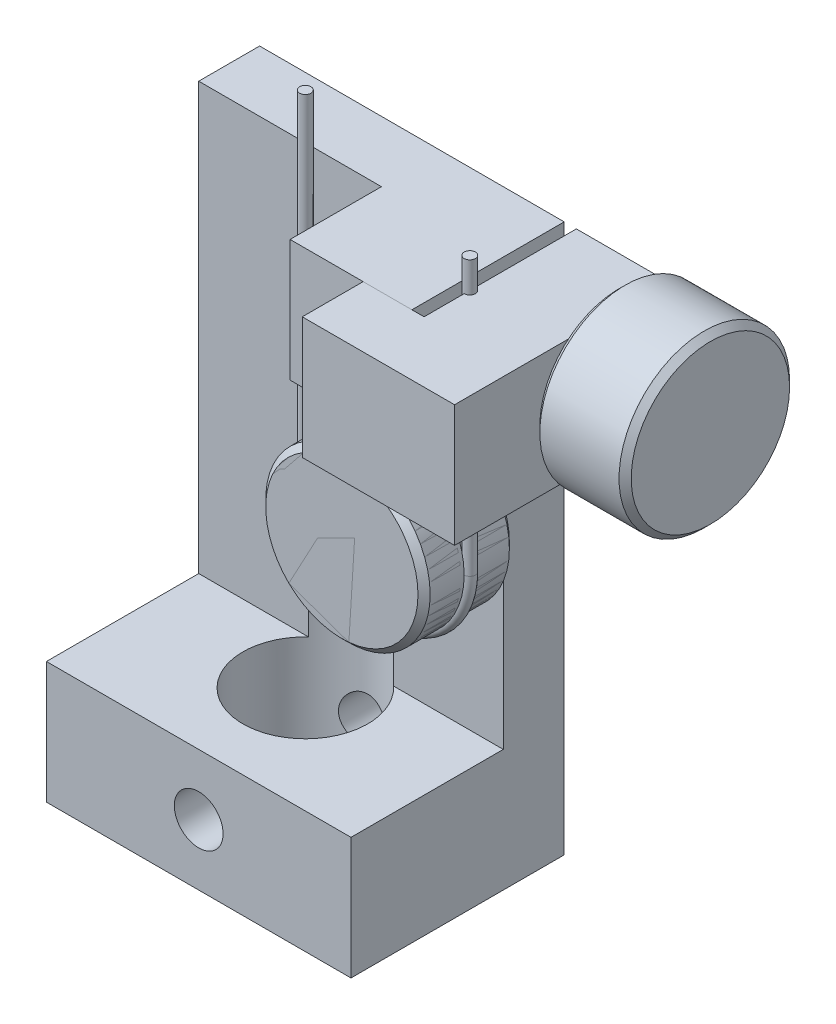
SolidWorks part; units mm, degrees
note: The reader was unsure of these and kept them because the rebuilt part matched: shared geometry of "Sketch5<3>", "Sketch10<3>", "Sketch14<5>", "Sketch19<3>".
other "Clamp"
other "Base"
other "2,85mm"
other "1,75mm"
other "Fastener"
ref_plane "Front Plane" through (0, 0, 0) normal (0, 0, 1) x (1, 0, 0)
ref_plane "Top Plane" through (0, 0, 0) normal (0, 1, 0) x (1, 0, 0)
ref_plane "Right Plane" through (0, 0, 0) normal (1, 0, 0) x (0, 0, -1)
sketch "Sketch1" plane through (0, 0, 0) normal (0, 0, 1) x (1, 0, 0)
  line L1 (25, -45) -> (-25, -45)
  line L2 (25, -45) -> (25, 45)
  line L3 (25, 45) -> (-25, 45)
  line L4 (-25, -45) -> (-25, 45)
  line L5 (0, 45) -> (0, -45) construction
  line L6 (25, 0) -> (-25, 0) construction
  point P0 (0, 0)
  dimension "D1" = 50
  dimension "D2" = 90
extrude "Boss-Extrude1" add sketch "Sketch1" along normal blind 10
sketch "Sketch2" plane through (0, 0, 10) normal (0, 0, 1) x (1, 0, 0)
  line L0 (-25, 45) -> (-25, -45) construction
  line L1 (-25, -25) -> (25, -25)
  line L2 (-25, -25) -> (-25, -45)
  line L3 (-25, -45) -> (25, -45)
  line L4 (25, -25) -> (25, -45)
  dimension "D1" = 20
extrude "Boss-Extrude2" add sketch "Sketch2" along normal blind 25
sketch "Sketch3" plane through (0, -25, 0) normal (0, 1, 0) x (1, 0, 0)
  line L1 (25, -10) -> (-25, -10) construction
  line L2 (0, 0) -> (0, -35) construction
  line L3 (25, 0) -> (-25, 0) construction
  line L4 (25, -35) -> (-25, -35) construction
  circle A0 centre (0, -17.5) radius 10.25
  point P9 (0, -10)
  dimension "D1" = 20.5
extrude "Cut-Extrude1" cut sketch "Sketch3" against normal through all and the other way blind 5
sketch "Sketch4" plane through (0, 0, 35) normal (0, 0, 1) x (1, 0, 0)
  line L0 (0, -25) -> (0, -45) construction
  line L2 (-25, -45) -> (25, -45) construction
  line L3 (25, -25) -> (-25, -25) construction
  circle A0 centre (0, -35) radius 4
  dimension "D1" = 8
  dimension "D2" = 10
extrude "Cut-Extrude2" cut sketch "Sketch4" against normal through all
sketch "Sketch5" plane through (0, 0, 10) normal (0, 0, 1) x (1, 0, 0)
  line L0 (0, -45) -> (0, 45) construction
  line L1 (-25, -45) -> (25, -45) construction
  line L2 (25, 45) -> (-25, 45) construction
  line L3 (25, -25) -> (25, 45) construction
  line L4 (25, 45) -> (5, 45)
  line L5 (25, 45) -> (25, 25)
  line L6 (25, 25) -> (5, 25)
  line L7 (5, 45) -> (5, 25)
  circle A0 centre (13.5, 5) radius 4.25
  circle A1 centre (13.5, 5) radius 12.075 construction
  line M9 (25, -25) -> (25, 45)
  line M10 (25, 45) -> (-25, 45)
  dimension "D1" = 8.5
  dimension "D5" = 1.425
  dimension "D2" = 20
  dimension "D3" = 20
  dimension "D4" = 20
  dimension "D6" = 11.5
extrude "Cut-Extrude3" cut sketch "Sketch5" against normal blind 30 contours A0
extrude "Boss-Extrude3" add sketch "Sketch5<3>" along normal blind 15 contours L7 L6 M10 M9
sketch "Sketch5<3>" plane through (0, 0, 10) normal (0, 0, 1) x (1, 0, 0) same geometry as "Sketch5"
sketch "Sketch9" plane through (0, 45, 0) normal (0, 1, 0) x (1, 0, 0)
  line L1 (27, 0) -> (42, 0)
  line L2 (27, 0) -> (27, -25)
  line L3 (27, -25) -> (42, -25)
  line L4 (42, 0) -> (42, -25)
  line L5 (25, 0) -> (-25, 0) construction
  line L6 (25, -25) -> (25, 0) construction
  line L7 (25, -25) -> (5, -25) construction
  dimension "D1" = 15
  dimension "D2" = 2
extrude "Boss-Extrude4" add sketch "Sketch9" against normal up to surface (20 mm away) separate body up to face at (15, 25, 17.5)
sketch "Sketch10" plane through (42, 0, 0) normal (1, 0, 0) x (0, 0, -1)
  line L0 (-22.5, -25) -> (-22.5, 45) construction
  line L1 (-35, -25) -> (-10, -25) construction
  line L2 (-25, 45) -> (0, 45) construction
  line L3 (0, -45) -> (0, 45) construction
  line L4 (-25, 25) -> (-25, 45) construction
  line L5 (-25, 35) -> (0, 35) construction
  line L6 (0, 25) -> (0, 45) construction
  line L7 (-17.5, 25) -> (-17.5, 45) construction
  line L8 (-25, 25) -> (-10, 25) construction
  line L9 (-25, 45) -> (0, 45) construction
  line L11 (-19, 45) -> (-16, 45) construction
  line L12 (-19, 45) -> (-19, 25) construction
  line L13 (-19, 25) -> (-16, 25) construction
  line L14 (-16, 45) -> (-16, 25) construction
  circle A0 centre (-8, 35) radius 4.25
  circle A1 centre (-8, 35) radius 5
  dimension "D1" = 8.5
  dimension "D4" = 10
  dimension "D2" = 8
  dimension "D3" = 3
extrude "Cut-Extrude4" cut sketch "Sketch10" against normal blind 27 contours A0
extrude "Cut-Extrude5" cut sketch "Sketch10<3>" against normal up to next (15 mm away)
sketch "Sketch10<3>" plane through (42, 0, 0) normal (1, 0, 0) x (0, 0, -1) same geometry as "Sketch10"
sketch "Sketch14" plane through (0, 0, 10) normal (0, 0, 1) x (1, 0, 0)
  line L0 (0, 45) -> (0, -45) construction
  line L1 (5, 45) -> (-25, 45) construction
  line L2 (-25, -45) -> (25, -45) construction
  circle A0 centre (13.5, 5) radius 13.5
  circle A3 centre (13.5, 5) radius 4.925
  circle M2 centre (13.5, 5) radius 4.25
  line M8 (25, -25) -> (25, 25)
  dimension "D1" = 27
  dimension "D2" = 9.85
extrude "Boss-Extrude5" add sketch "Sketch14" along normal up to surface (15 mm away) separate body contours M2 | A3 M2 | A0 A3 M8
extrude "Boss-Extrude8" add sketch "Sketch14<5>" against normal up to surface (10 mm away) contours M2 | A3 M2 up to face at (17.75, 5, 0)
sketch "Sketch14<5>" plane through (0, 0, 10) normal (0, 0, 1) x (1, 0, 0) same geometry as "Sketch14"
sketch "Sketch16" plane through (0, 0, 25) normal (0, 0, 1) x (1, 0, 0)
  line L0 (27, 5) -> (0, 5) construction
  circle A0 centre (13.5, 5) radius 13.5 construction
ref_plane "Plane4" through (0, 5, 0) normal (0, 1, 0) x (-1, 0, 0)
sketch "Sketch17" plane through (0, 5, 0) normal (0, 1, 0) x (-1, 0, 0)
  line L0 (0, 17.5) -> (-27, 17.5) construction
  line L1 (0, 10) -> (0, 25) construction
  line L2 (-27, 25) -> (-27, 10) construction
  line L3 (0, 18.425) -> (0, 17.5) construction
  line L6 (-13.5, 25) -> (-13.5, 0) construction
  line L7 (-27, 25) -> (0, 25) construction
  line L8 (-25, 0) -> (25, 0) construction
  line L9 (0, 18.425) -> (0, 16.575)
  arc A0 (0, 18.425) -> (0, 16.575) centre (0, 17.5) ccw
  dimension "D1" = 1.85
revolve "Cut-Revolve1" cut sketch "Sketch17" angle 360 about L6
sketch "Sketch18" plane through (0, 0, 10) normal (0, 0, 1) x (1, 0, 0)
  line L0 (0, -20) -> (0, 45) construction
  line L1 (6.9866, -20) -> (-6.9866, -20) construction
  line L2 (5, 45) -> (-25, 45) construction
sketch "Sketch19" plane through (0, 0, 10) normal (0, 0, 1) x (1, 0, 0)
  line L0 (27, 5) -> (0, 5) construction
  circle A0 centre (13.5, 5) radius 13.5
  circle A3 centre (13.5, 5) radius 4.925
  circle M2 centre (13.5, 5) radius 4.25
  line M12 (25, -25) -> (25, 25)
  dimension "D1" = 27
  dimension "D2" = 9.85
extrude "Boss-Extrude7" add sketch "Sketch19" along normal up to surface (15 mm away) separate body contours A0 M12 | M2 | A3 M2 | A0 A3 M12 up to face at (15, 35, 25)
extrude "Boss-Extrude9" add sketch "Sketch19<3>" against normal up to surface (10 mm away) contours M2 | A3 M2 up to face at (17.75, 5, 0)
sketch "Sketch19<3>" plane through (0, 0, 10) normal (0, 0, 1) x (1, 0, 0) same geometry as "Sketch19"
sketch "Sketch20" plane through (0, 5, 0) normal (0, 1, 0) x (-1, 0, 0)
  line L0 (0, 17.5) -> (-27, 17.5) construction
  line L1 (0, 10) -> (0, 25) construction
  line L3 (-27, 25) -> (-27, 10) construction
  line L4 (-13.5, 25) -> (-13.5, 17.5) construction
  line L5 (0, 25) -> (-27, 25) construction
  line L6 (0, 18.975) -> (0, 16.025)
  arc A0 (0, 18.975) -> (0, 16.025) centre (0, 17.5) ccw
  dimension "D1" = 2.95
revolve "Cut-Revolve2" cut sketch "Sketch20" angle 360 about L4
hole_wizard "Ø1.0mm Dowel Hole1" positions "3DSketch1" profile "Sketch23" hole size "Ø1.0" standard "ANSI Metric"
sketch3d "3DSketch1"
  line L0 (15, 35, 8) -> (25, 35, 8) construction
  point P0 (15, 35, 8)
sketch "Sketch23" plane through (15, 35, 8) normal (0, 1, 0) x (0, 0, -1)
  line L0 (0, 0) -> (0, 7.5537)
  line L1 (0, 7.5537) -> (4.25, 5)
  line L2 (4.25, 5) -> (4.25, 0)
  line L5 (4.25, 0) -> (0, 0)
  line L10 (0, 7.5537) -> (-4.25, 5) construction
  line L11 (0, -6.35) -> (0, 107.95) construction
  dimension "Hole Dia." = 8.5
  dimension "Hole Depth" = 5
  dimension "Drill Angle" = 118
sketch "Sketch24" plane through (0, 5, 0) normal (0, 1, 0) x (-1, 0, 0)
  line L0 (-18.425, 9) -> (-8.575, 9) construction
  line L1 (-18.425, 10) -> (-18.425, 0) construction
  line L2 (-8.575, 0) -> (-8.575, 10) construction
  line L3 (-8.575, 10) -> (-8.575, 8)
  line L4 (-27, 10) -> (0, 10) construction
  line L5 (-13.5, 9) -> (-13.5, 0) construction
  line L6 (-18.425, 0) -> (-8.575, 0) construction
  arc A0 (-8.575, 10) -> (-8.575, 8) centre (-8.575, 9) ccw
  dimension "D1" = 2
revolve "Cut-Revolve3" cut sketch "Sketch24" angle 360 about L5
chamfer "Chamfer1" distance 1 angle 45 3 edges at (27, 5, 25) (27, 5, 10) (18.425, 5, 0)
chamfer "Chamfer2" distance 1 angle 45 3 edges at (18.425, 5, 0) (27, 5, 25) (27, 5, 10)
sketch "Sketch25" plane through (0, 5, 0) normal (0, 1, 0) x (-1, 0, 0)
  line L0 (-18.425, 9) -> (-8.575, 9) construction
  line L1 (-18.425, 10) -> (-18.425, 1) construction
  line L2 (-8.575, 1) -> (-8.575, 10) construction
  line L3 (-13.5, 9) -> (-13.5, 0) construction
  line L4 (-17.425, 0) -> (-9.575, 0) construction
  line L5 (-8.575, 10) -> (-8.575, 8)
  line L6 (-18.425, 10) -> (-8.575, 10) construction
  arc A0 (-8.575, 10) -> (-8.575, 8) centre (-8.575, 9) ccw
  dimension "D1" = 1
revolve "Cut-Revolve4" cut sketch "Sketch25" angle 360 about L3
sketch "Sketch26" plane through (42, 0, 0) normal (1, 0, 0) x (0, 0, -1)
  circle A0 centre (-8, 35) radius 14
  dimension "D1" = 28
extrude "Boss-Extrude10" add sketch "Sketch26" along normal blind 15 separate body
sketch "Sketch27" plane through (42, 0, 0) normal (-1, 0, 0) x (0, 0, 1)
  circle A2 centre (8, 35) radius 4.925
  dimension "D1" = 9.85
extrude "Boss-Extrude11" add sketch "Sketch27" along normal blind 27
sketch "Sketch28" plane through (0, 0, 25) normal (0, 0, 1) x (1, 0, 0)
  line L0 (57, 35) -> (5, 35) construction
  line L1 (57, 21) -> (57, 49) construction
  line L2 (5, 45) -> (5, 25) construction
ref_plane "Plane5" through (0, 35, 0) normal (0, 1, 0) x (-1, 0, 0)
sketch "Sketch29" plane through (0, 35, 0) normal (0, 1, 0) x (-1, 0, 0)
  line L0 (-57, 8) -> (-25, 8) construction
  line L1 (-57, 22) -> (-57, -6) construction
  line L2 (-25, 25) -> (-25, 0) construction
  line L4 (-42, 12.925) -> (-26, 12.925)
  line L5 (-42, 12.925) -> (-42, 12)
  line L6 (-42, 12) -> (-26, 12)
  line L7 (-26, 12.925) -> (-26, 12)
  dimension "D1" = 16
  dimension "D2" = 0.925
revolve "Cut-Revolve5" cut sketch "Sketch29" angle 360 about L0
chamfer "Chamfer3" distance 1 angle 45 3 edges at (57, 35, -6) (42, 35, -6) (15, 35, 12.925)
sketch "Sketch30" plane through (42, 0, 0) normal (1, 0, 0) x (0, 0, -1)
  line L0 (0, 35) -> (-8, 35) construction
  line L1 (0, 25) -> (0, 45) construction
  line L2 (-8, 35) -> (-8, 25) construction
  line L3 (-25, 25) -> (0, 25) construction
sketch "Sketch31" plane through (0, 45, 0) normal (0, 1, 0) x (1, 0, 0)
  line L0 (27, -25) -> (17, -25)
  line L1 (17, -25) -> (17, -35)
  line L2 (17, -35) -> (42, -35)
  line L3 (42, -35) -> (42, -25)
  line L4 (27, -25) -> (42, -25) construction
  line L5 (42, -25) -> (42, 0) construction
  line L10 (27, 0) -> (27, -25)
  line L11 (27, -25) -> (42, -25)
  line L12 (42, -25) -> (42, 0)
  line L13 (42, 0) -> (27, 0)
  line L15 (27, -25) -> (42, -25)
  dimension "D1" = 10
  dimension "D2" = 25
  dimension "D3" = 0
extrude "Boss-Extrude12" add sketch "Sketch31" against normal up to surface (20 mm away) up to face at (34.5, 25, 12.5)
other "Save Bodies1"
other "Save Bodies2"
ref_plane "Plane6" through (-35, 0, 0) normal (-1, 0, 0) x (0, 0, 1)
ref_plane "Plane7" through (0, 50, 0) normal (0, 1, 0) x (1, 0, 0)
sketch "Sketch32" plane through (0, 50, 0) normal (0, 1, 0) x (1, 0, 0)
  line L0 (27, 0) -> (27, -25) construction
  circle A0 centre (27, -17.5) radius 0.925
  arc A1 (27, -16.575) -> (27, -18.425) centre (27, -17.5) ccw construction
ref_plane "Plane8" through (0, 0, 17.5) normal (0, 0, 1) x (1, 0, 0)
sketch "Sketch33" plane through (0, 0, 17.5) normal (0, 0, 1) x (1, 0, 0)
  line L0 (27, 50) -> (27, 5)
  line L1 (27.925, 50) -> (26.075, 50) construction
  line L2 (0, 5) -> (0, 60)
  line L3 (5, 45) -> (-25, 45) construction
  circle A0 centre (13.5, 5) radius 13.5 construction
  arc A1 (0, 5) -> (27, 5) centre (13.5, 5) ccw
  dimension "D1" = 15
sweep "Sweep1" add profiles "Sketch32" path "Sketch33"
